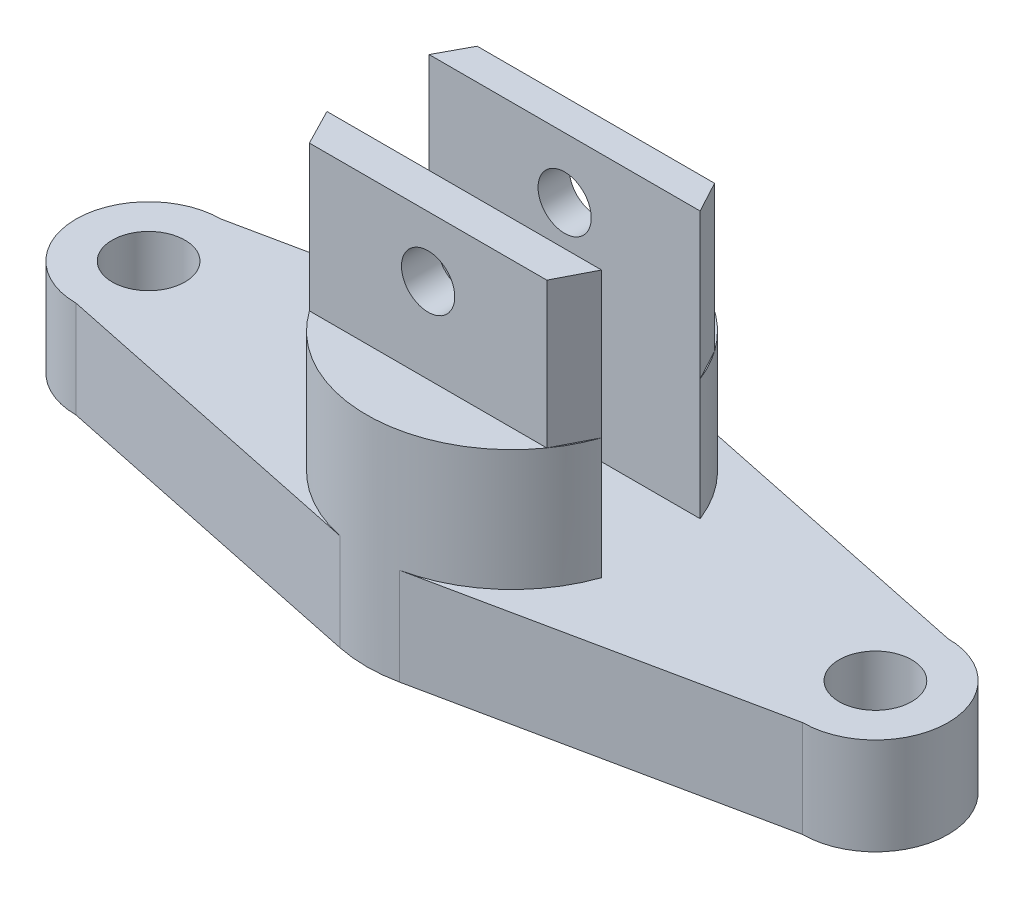
SolidWorks part; units mm, degrees
ref_plane "Alzado" through (0, 0, 0) normal (0, 0, 1) x (1, 0, 0)
ref_plane "Planta" through (0, 0, 0) normal (0, 1, 0) x (1, 0, 0)
ref_plane "Vista lateral" through (0, 0, 0) normal (1, 0, 0) x (0, 0, -1)
sketch "Croquis2" plane through (0, 0, 0) normal (0, 1, 0) x (1, 0, 0)
  line L0 (-75, 15) -> (-6.1264, 29.3678)
  line L1 (-75, -15) -> (-6.1264, -29.3678)
  line L3 (75, -15) -> (6.1264, -29.3678)
  line L4 (75, 15) -> (6.1264, 29.3678)
  line L6 (0, 0) -> (12.8592, 0) construction
  arc A1 (-75, 15) -> (-75, -15) centre (-75, 0) ccw
  arc A2 (75, 15) -> (75, -15) centre (75, 0) cw
  circle A4 centre (-75, 0) radius 7.5
  circle A5 centre (75, 0) radius 7.5
  arc A6 (-6.1264, -29.3678) -> (6.1264, -29.3678) centre (0, 0) ccw
  arc A7 (6.1264, 29.3678) -> (-6.1264, 29.3678) centre (0, 0) ccw
  dimension "D2" = 30
  dimension "D4" = 15
  dimension "D5" = 15
  dimension "D3" = 75
extrude "Saliente-Extruir3" add sketch "Croquis2" along normal blind 20
sketch "Croquis6" plane through (0, 20, 0) normal (0, 1, 0) x (1, 0, 0)
  line L2 (0, 0) -> (20.3158, 0) construction
  circle A0 centre (0, 0) radius 30
  point P12 (0, 0)
  dimension "D2" = 60
extrude "Saliente-Extruir4" add sketch "Croquis6" along normal blind 25 contours A0
sketch "Croquis9" plane through (0, 0, 0) normal (1, 0, 0) x (0, 0, -1)
  line L0 (30, 45) -> (-30, 45) construction
  line L1 (-9.8562, 45) -> (10.8619, 45)
  line L2 (-9.8562, 45) -> (-9.8562, 20)
  line L3 (-9.8562, 20) -> (10.8619, 20)
  line L4 (10.8619, 45) -> (10.8619, 20)
  line L5 (29.3678, 20) -> (-29.3678, 20) construction
extrude "Cortar-Extruir1" cut sketch "Croquis9" against normal blind 31 and the other way blind 35
sketch "Croquis10" plane through (0, 45, 0) normal (0, 1, 0) x (1, 0, 0)
  line L0 (-24.5006, 17.3124) -> (24.5006, 17.3124)
  line L1 (24.5006, 17.3124) -> (27.9646, 10.8619)
  line L2 (27.9646, 10.8619) -> (-27.9646, 10.8619)
  line L3 (-27.9646, 10.8619) -> (-24.5006, 17.3124)
  line L4 (0, 0) -> (16.8963, 0) construction
  line L5 (-28.3347, -9.8562) -> (-24.5006, -17.3124)
  line L6 (-24.5006, -17.3124) -> (24.5006, -17.3124)
  line L7 (24.5006, -17.3124) -> (28.3347, -9.8562)
  line L8 (28.3347, -9.8562) -> (-28.3347, -9.8562)
  arc A2 (27.9646, 10.8619) -> (-27.9646, 10.8619) centre (0, 0) ccw construction
  arc A3 (27.9646, 10.8619) -> (6.1264, 29.3678) centre (0, 0) ccw construction
  arc A4 (-28.3347, -9.8562) -> (28.3347, -9.8562) centre (0, 0) ccw construction
  arc A5 (6.1264, -29.3678) -> (28.3347, -9.8562) centre (0, 0) ccw construction
extrude "Saliente-Extruir5" add sketch "Croquis10" along normal blind 30
sketch "Croquis11" plane through (0, 0, 17.3124) normal (0, 0, 1) x (1, 0, 0)
  circle A0 centre (0, 62.5115) radius 5.4924
extrude "Cortar-Extruir2" cut sketch "Croquis11" against normal blind 38 and the other way blind 15
